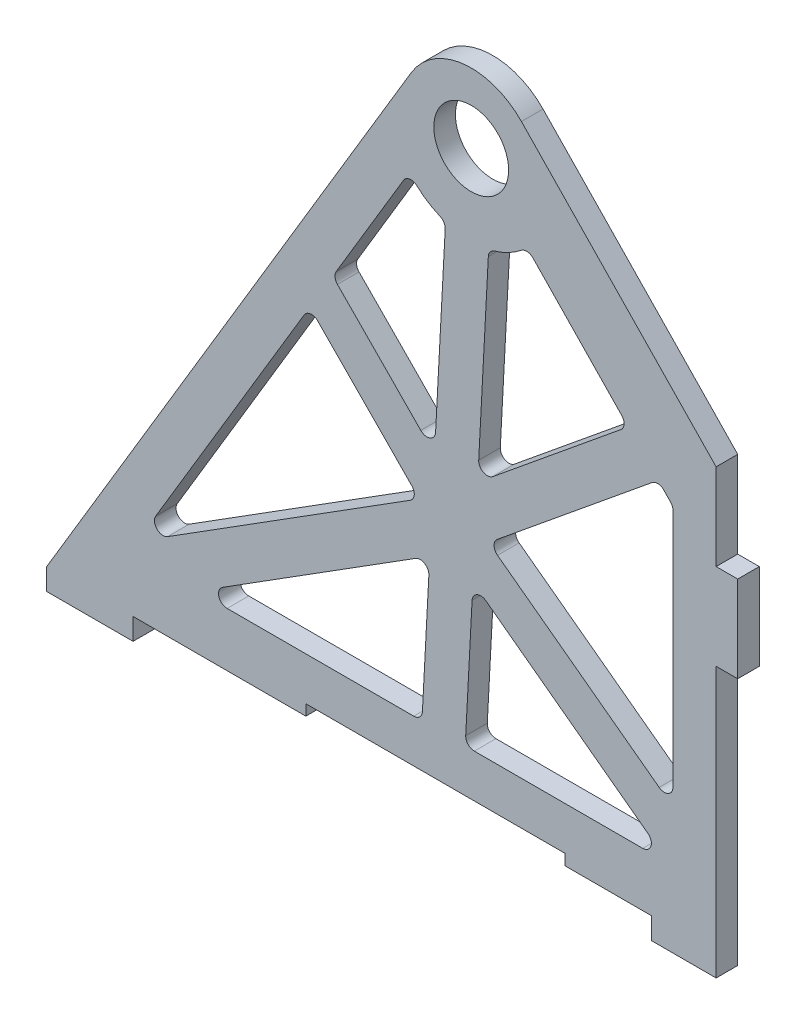
SolidWorks part; units mm, degrees
ref_plane "Front Plane" through (0, 0, 0) normal (0, 0, 1) x (1, 0, 0)
ref_plane "Top Plane" through (0, 0, 0) normal (0, 1, 0) x (1, 0, 0)
ref_plane "Right Plane" through (0, 0, 0) normal (1, 0, 0) x (0, 0, -1)
sketch "Sketch2" plane through (0, 0, 0) normal (0, 0, 1) x (1, 0, 0)
  line L0 (1566.672, 2.5421) -> (1649.222, 2.5421) construction
  line L1 (1592.072, 2.5421) -> (1642.872, 2.5421)
  line L2 (1566.672, 2.5421) -> (1673.8864, 181.9515)
  line L4 (1642.872, 2.5421) -> (1642.872, 5.7171)
  line L6 (1566.672, 2.5421) -> (1566.672, -3.8079)
  line L7 (1566.672, -3.8079) -> (1592.072, -3.8079)
  line L8 (1592.072, 2.5421) -> (1592.072, -3.8079)
  line L13 (1642.872, 5.7171) -> (1719.072, 5.7171)
  line L14 (1719.072, 5.7171) -> (1719.072, 2.5421)
  line L16 (1719.072, 2.5421) -> (1744.472, 2.5421)
  line L17 (1566.672, -33.6061) -> (1769.872, -33.6061) construction
  line L18 (1744.472, 2.5421) -> (1744.472, -3.8079)
  line L19 (1744.472, -3.8079) -> (1763.522, -3.8079)
  line L20 (1763.522, -3.8079) -> (1763.522, 75.5671)
  line L22 (1763.522, 126.3671) -> (1706.2728, 185.6771)
  line L23 (1763.522, 100.9671) -> (1763.522, 126.3671)
  line L24 (1763.522, 100.9671) -> (1769.872, 100.9671)
  line L26 (1763.522, 75.5671) -> (1769.872, 75.5671)
  line L27 (1769.872, 100.9671) -> (1769.872, 75.5671)
  arc A0 (1706.2728, 185.6771) -> (1673.8864, 181.9515) centre (1691.5051, 171.4226) ccw
  circle A1 centre (1691.5051, 171.4226) radius 11 construction
  circle A2 centre (1691.5051, 171.4226) radius 4 construction
  circle A3 centre (1691.5051, 171.4226) radius 11
  dimension "D3" = 22
  dimension "D4" = 9.525
  dimension "D5" = 8
  dimension "D6" = 22
  dimension "D1" = 168.8805
  dimension "D2" = 124.8331
  dimension "D7" = 6.35
  dimension "D8" = 25.4
  dimension "D9" = 19.05
  dimension "D10" = 6.35
  dimension "D11" = 44.45
  dimension "D12" = 203.2
  dimension "D13" = 76.2
  dimension "D14" = 3.175
  dimension "D15" = 130.175
  dimension "D16" = 6.35
  dimension "D17" = 25.4
  dimension "D18" = 25.4
extrude "Boss-Extrude1" add sketch "Sketch2" along normal blind 6.35
sketch "Sketch4" plane through (0, 0, 6.35) normal (0, 0, 1) x (1, 0, 0)
  line L0 (1673.3123, 156.2334) -> (1577.5737, -3.9728)
  line L1 (1691.5051, 171.4226) -> (1750.822, 109.9704)
  line L2 (1684.7881, 175.4367) -> (1577.5737, -3.9728) construction
  line L3 (1590.9538, 18.4171) -> (1750.822, 18.4171)
  line L4 (1686.3016, 73.3904) -> (1617.2071, 143.6449) construction
  line L7 (1681.7742, 68.9378) -> (1612.6797, 139.1923)
  line L10 (1690.8289, 77.843) -> (1621.7344, 148.0975)
  line L13 (1566.672, 2.5421) -> (1566.672, -3.8079)
  line L14 (1566.672, -3.8079) -> (1592.072, -3.8079)
  line L15 (1592.072, -3.8079) -> (1592.072, 2.5421)
  line L16 (1592.072, 2.5421) -> (1642.872, 2.5421)
  line L17 (1642.872, 2.5421) -> (1642.872, 5.7171)
  line L18 (1642.872, 5.7171) -> (1719.072, 5.7171)
  line L19 (1719.072, 5.7171) -> (1719.072, 2.5421)
  line L20 (1719.072, 2.5421) -> (1744.472, 2.5421)
  line L21 (1744.472, -3.8079) -> (1763.522, -3.8079)
  line L22 (1744.472, 2.5421) -> (1744.472, -3.8079)
  line L23 (1719.072, 2.5421) -> (1744.472, 2.5421)
  line L24 (1763.522, -3.8079) -> (1763.522, 75.5671)
  line L25 (1673.8864, 181.9515) -> (1566.672, 2.5421)
  line L26 (1566.672, 2.5421) -> (1566.672, -3.8079)
  line L27 (1566.672, -3.8079) -> (1592.072, -3.8079)
  line L28 (1592.072, -3.8079) -> (1592.072, 2.5421)
  line L29 (1592.072, 2.5421) -> (1642.872, 2.5421)
  line L30 (1642.872, 2.5421) -> (1642.872, 5.7171)
  line L31 (1642.872, 5.7171) -> (1719.072, 5.7171)
  line L32 (1719.072, 5.7171) -> (1719.072, 2.5421)
  line L34 (1744.472, -3.8079) -> (1763.522, -3.8079)
  line L35 (1744.472, 2.5421) -> (1744.472, -3.8079)
  line L38 (1673.8864, 181.9515) -> (1566.672, 2.5421)
  line L39 (1686.3016, 73.3904) -> (1776.688, 147.3217) construction
  line L42 (1682.2812, 78.3056) -> (1772.6676, 152.2368)
  line L45 (1690.3219, 68.4752) -> (1780.7084, 142.4065)
  line L46 (1686.3016, 73.3904) -> (1535.3984, -21.6576) construction
  line L47 (1750.822, 109.9704) -> (1750.822, 18.4171)
  line L48 (1689.6858, 68.0174) -> (1538.7827, -27.0307)
  line L49 (1682.9173, 78.7634) -> (1532.0142, -16.2846)
  line L50 (1686.3016, 73.3904) -> (1767.8024, 12.8123) construction
  line L51 (1690.0896, 78.4868) -> (1771.5905, 17.9087)
  line L52 (1682.5135, 68.294) -> (1764.0144, 7.7159)
  line L53 (1691.5051, 171.4226) -> (1681.8948, -9.6316) construction
  line L54 (1697.8462, 171.086) -> (1688.2358, -9.9682)
  line L55 (1685.1641, 171.7592) -> (1675.5537, -9.2951)
  line L60 (1763.522, -3.8079) -> (1763.522, 75.5671)
  line L61 (1763.522, 126.3671) -> (1706.2728, 185.6771)
  line L62 (1763.522, 126.3671) -> (1706.2728, 185.6771)
  line L68 (1763.522, 75.5671) -> (1769.872, 75.5671)
  line L69 (1763.522, 75.5671) -> (1769.872, 75.5671)
  line L70 (1769.872, 75.5671) -> (1769.872, 100.9671)
  line L71 (1769.872, 75.5671) -> (1769.872, 100.9671)
  line L72 (1769.872, 100.9671) -> (1763.522, 100.9671)
  line L73 (1769.872, 100.9671) -> (1763.522, 100.9671)
  line L74 (1763.522, 100.9671) -> (1763.522, 126.3671)
  line L75 (1763.522, 100.9671) -> (1763.522, 126.3671)
  arc A1 (1706.2728, 185.6771) -> (1673.8864, 181.9515) centre (1691.5051, 171.4226) ccw
  arc A2 (1706.2728, 185.6771) -> (1673.8864, 181.9515) centre (1691.5051, 171.4226) ccw
  circle A4 centre (1691.5051, 171.4226) radius 23.7
  circle A5 centre (1691.5051, 171.4226) radius 23.7
  arc A14 (1681.7742, 68.9378) -> (1690.8289, 77.843) centre (1686.3016, 73.3904) ccw
  arc A15 (1621.7344, 148.0975) -> (1612.6797, 139.1923) centre (1617.2071, 143.6449) ccw
  arc A16 (1682.2812, 78.3056) -> (1690.3219, 68.4752) centre (1686.3016, 73.3904) ccw
  arc A17 (1780.7084, 142.4065) -> (1772.6676, 152.2368) centre (1776.688, 147.3217) ccw
  arc A18 (1689.6858, 68.0174) -> (1682.9173, 78.7634) centre (1686.3016, 73.3904) ccw
  arc A19 (1532.0142, -16.2846) -> (1538.7827, -27.0307) centre (1535.3984, -21.6576) ccw
  arc A20 (1690.0896, 78.4868) -> (1682.5135, 68.294) centre (1686.3016, 73.3904) ccw
  arc A21 (1764.0144, 7.7159) -> (1771.5905, 17.9087) centre (1767.8024, 12.8123) ccw
  arc A22 (1697.8462, 171.086) -> (1685.1641, 171.7592) centre (1691.5051, 171.4226) ccw
  arc A23 (1675.5537, -9.2951) -> (1688.2358, -9.9682) centre (1681.8948, -9.6316) ccw
  point P15 (1651.7543, 108.5176)
  point P28 (1731.4948, 110.356)
  point P35 (1610.85, 25.8664)
  point P42 (1727.052, 43.1013)
  point P50 (1686.6999, 80.8955)
  dimension "D6" = 6.35
  dimension "D4" = 12.7
  dimension "D5" = 12.7
  dimension "D1" = 0
  dimension "D2" = 12.7
  dimension "D3" = 12.7
extrude "Cut-Extrude1" cut sketch "Sketch4" against normal through all contours L49 L7 L0 | A5 L0 L10 L55 | A5 L54 L42 L1 | L45 L51 L47 L1 | L52 L54 L3 | L55 L48 L3 region at (1671.2173, 123.5261, 6.35) region at (1637.86, 68.0487, 6.35) region at (1710.0985, 123.4313, 6.35) region at (1655.7577, 32.7722, 6.35) region at (1732.6302, 74.6826, 6.35) region at (1710.4583, 32.6886, 6.35)
fillet "Fillet1" radius 2.54 21 edges at (1673.3123, 156.2334, 3.175) (1593.2749, 22.3011, 3.175) (1707.9647, 154.3705, 3.175) (1750.822, 109.9704, 3.175) (1746.512, 114.4356, 3.175) (1750.822, 33.3455, 3.175) (1696.624, 73.6299, 3.175) (1737.662, 123.6041, 3.175) (1693.4043, 87.4037, 3.175) (1696.6359, 148.2846, 3.175) (1677.0247, 18.4171, 3.175) (1610.9378, 18.4171, 3.175) (1679.3106, 61.4824, 3.175) (1644.0607, 107.2845, 3.175) (1676.2444, 74.5604, 3.175) (1683.9538, 148.9578, 3.175) (1650.7933, 118.5507, 3.175) (1749.6172, 18.4171, 3.175) (1689.7425, 18.4171, 3.175) (1692.0151, 61.2316, 3.175) (1680.7243, 88.1172, 3.175)
